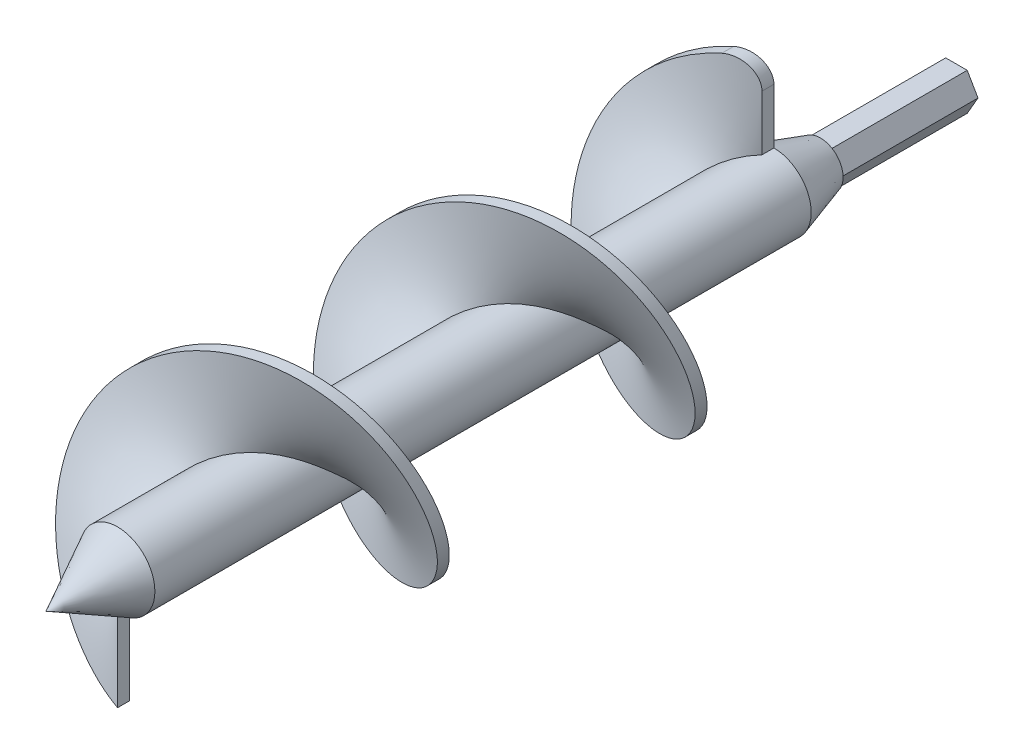
SolidWorks part; units mm, degrees
ref_plane "Front Plane" through (0, 0, 0) normal (1, 0, 0) x (0, 1, 0)
ref_plane "Top Plane" through (0, 0, 0) normal (0, 0, 1) x (0, 1, 0)
ref_plane "Right Plane" through (0, 0, 0) normal (0, 1, 0) x (-1, 0, 0)
sketch "Sketch6" plane through (0, 0, 0) normal (1, 0, 0) x (0, 1, 0)
  line L0 (-7.9375, 139.7) -> (0, 154.94)
  line L1 (0, 0) -> (-7.9375, 0)
  line L2 (0, 0) -> (0, 139.7)
  line L3 (0, 139.7) -> (-7.9375, 139.7)
  line L4 (-7.9375, 0) -> (-7.9375, 139.7)
  line L5 (0, 154.94) -> (0, 139.7)
  line L6 (0, 0) -> (0, -9.906)
  line L7 (0, -9.906) -> (-4.826, -9.906)
  line L8 (-4.826, -9.906) -> (-7.9375, 0)
  dimension "D1" = 139.7
  dimension "D2" = 7.9375
  dimension "D3" = 15.24
  dimension "D4" = 9.906
  dimension "D5" = 4.826
revolve "Revolve1" add sketch "Sketch6" angle 360 about L2
sketch "Sketch12" plane through (0, 0, -9.906) normal (0, 0, -1) x (1, 0, 0)
  line L0 (-4.826, 0) -> (4.826, 0) construction
  line L1 (4.5827, 0) -> (2.2914, 3.9688)
  line L2 (2.2914, 3.9688) -> (-2.2914, 3.9688)
  line L3 (-2.2914, 3.9688) -> (-4.5827, 0)
  line L4 (-4.5827, 0) -> (-2.2914, -3.9687)
  line L5 (-2.2914, -3.9687) -> (2.2914, -3.9687)
  line L6 (2.2914, -3.9687) -> (4.5827, 0)
  circle A0 centre (0, 0) radius 3.9687 construction
  circle A1 centre (0, 0) radius 4.826 construction
  dimension "D1" = 7.9375
extrude "Boss-Extrude1" add sketch "Sketch12" along normal blind 28.956
ref_plane "Plane1" through (0, 0, 0) normal (0, 0, -1) x (-1, 0, 0)
sketch "Sketch11" plane through (0, 0, 0) normal (0, 0, -1) x (1, 0, 0)
  circle A0 centre (0, 0) radius 25.4
  dimension "D1" = 50.8
curve "Helix/Spiral1" pitch 54.864 height 137.16 turns 2.5
sketch "Sketch14" plane through (0, 0, 0) normal (1, 0, 0) x (0, 1, 0)
  line L0 (7.9375, 0) -> (25.4, 0)
  line L1 (-8.7312, 0) -> (8.7312, 0) construction
  line L2 (7.9375, 0) -> (7.9375, 139.7) construction
  line L3 (25.4, 0) -> (25.4, 2.54)
  line L4 (25.4, 2.54) -> (7.9375, 2.54)
  line L5 (7.9375, 2.54) -> (7.9375, 0)
  spline S0 degree 3 poles (25.4, 0) (25.4, 0.7998) (24.7529, 2.4074) (21.9144, 4.8123) (17.4221, 7.219) (11.615, 9.6252) (4.9315, 12.0316) (-2.1242, 14.4379) (-9.0196, 16.8442) (-15.2344, 19.2505) (-20.2995, 21.6568) (-23.8327, 24.0632) (-25.5674, 26.4695) (-25.3727, 28.8758) (-23.2633, 31.2821) (-19.3983, 33.6884) (-14.0694, 36.0947) (-7.6789, 38.5011) (-0.7088, 40.9074) (6.3148, 43.3137) (12.8618, 45.72) (18.4382, 48.1263) (22.6232, 50.5326) (25.1009, 52.9389) (25.6845, 55.3453) (24.3298, 57.7516) (21.139, 60.1579) (16.3531, 62.5642) (10.333, 64.9705) (3.5332, 67.3768) (-3.5332, 69.7832) (-10.333, 72.1895) (-16.3531, 74.5958) (-21.139, 77.0021) (-24.3298, 79.4084) (-25.6845, 81.8147) (-25.1009, 84.2211) (-22.6232, 86.6274) (-18.4382, 89.0337) (-12.8618, 91.44) (-6.3148, 93.8463) (0.7088, 96.2526) (7.6789, 98.6589) (14.0694, 101.0653) (19.3983, 103.4716) (23.2633, 105.8779) (25.3727, 108.2842) (25.5674, 110.6905) (23.8327, 113.0968) (20.2995, 115.5032) (15.2344, 117.9095) (9.0196, 120.3158) (2.1242, 122.7221) (-4.9315, 125.1284) (-11.615, 127.5348) (-17.4221, 129.941) (-21.9144, 132.3477) (-24.7529, 134.7526) (-25.4, 136.3602) (-25.4, 137.16) knots 0 0 0 0 0.017544 0.035088 0.052632 0.070175 0.087719 0.105263 0.122807 0.140351 0.157895 0.175439 0.192982 0.210526 0.22807 0.245614 0.263158 0.280702 0.298246 0.315789 0.333333 0.350877 0.368421 0.385965 0.403509 0.421053 0.438596 0.45614 0.473684 0.491228 0.508772 0.526316 0.54386 0.561404 0.578947 0.596491 0.614035 0.631579 0.649123 0.666667 0.684211 0.701754 0.719298 0.736842 0.754386 0.77193 0.789474 0.807018 0.824561 0.842105 0.859649 0.877193 0.894737 0.912281 0.929825 0.947368 0.964912 0.982456 1 1 1 1 construction
  dimension "D1" = 2.54
sweep "Sweep2" add profiles "Sketch14" path "Helix/Spiral1"
fillet "Fillet2" radius 5.08 1 edges at (0, 25.4, 1.27)
